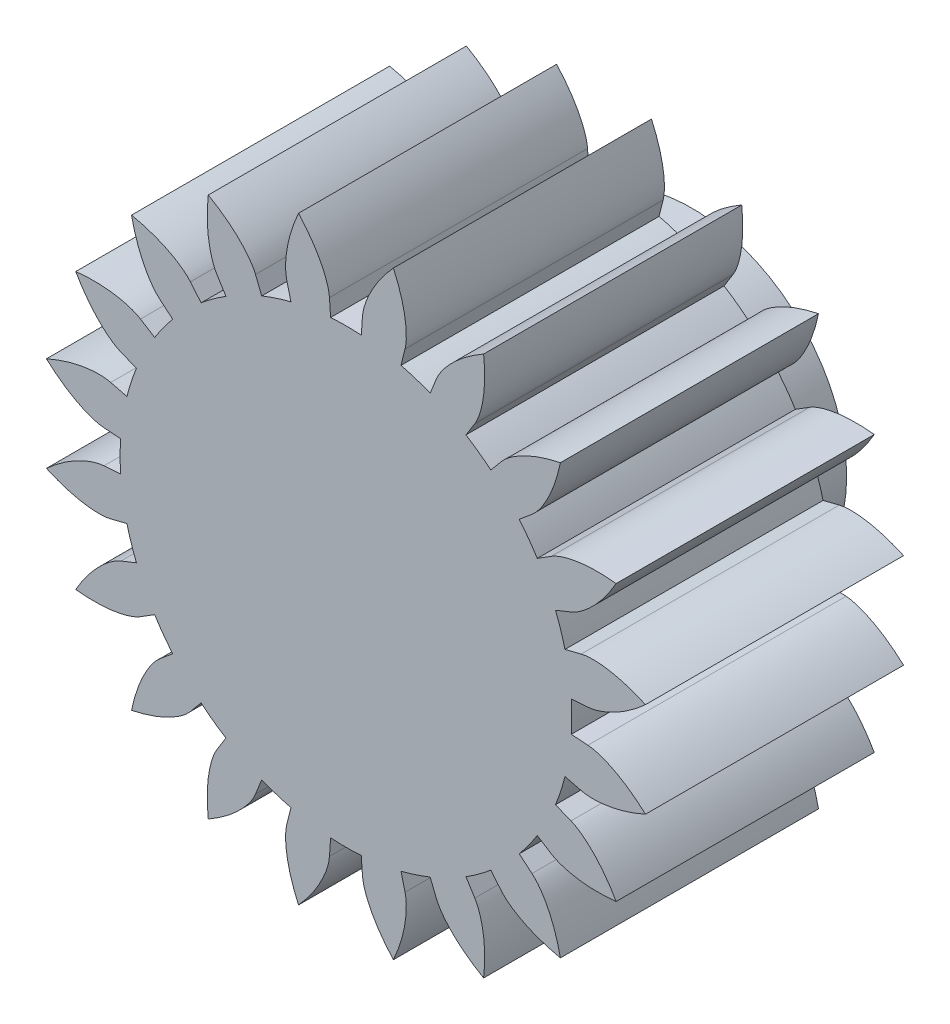
SolidWorks part; units mm, degrees
ref_plane "前视基准面" through (0, 0, 0) normal (0, 0, 1) x (1, 0, 0)
ref_plane "上视基准面" through (0, 0, 0) normal (0, 1, 0) x (1, 0, 0)
ref_plane "右视基准面" through (0, 0, 0) normal (1, 0, 0) x (0, 0, -1)
other "Configuration Table"
sketch "草图1" plane through (0, 0, 0) normal (0, 0, 1) x (1, 0, 0)
  line L0 (0, 0) -> (5, 0) construction
  line L1 (0, 0) -> (4.9846, 0.3923) construction
  line L2 (0, 0) -> (4.6876, 0.3194)
  line L3 (4.9846, 0.3923) -> (4.9846, -0.3923) construction
  line L4 (0, 0) -> (4.6876, -0.3194)
  circle A0 centre (0, 0) radius 5.5
  circle A1 centre (0, 0) radius 5 construction
  circle A2 centre (0, 0) radius 4.375
  circle A3 centre (0, 0) radius 4.6985 construction
  circle A4 centre (0, 0) radius 1.475
  circle A5 centre (0, 0) radius 6.5
  spline S0 degree 4 poles (4.6876, 0.3194) (4.7233, 0.3218) (4.8225, 0.336) (5.0062, 0.3926) (5.2885, 0.5242) (5.6241, 0.7499) (6.0094, 1.0976) (6.395, 1.5688) (6.7398, 2.1414) (7.0933, 2.9696) (7.3065, 3.8467) (7.3947, 4.7795) (7.347, 5.8934) (7.1568, 6.9938) (6.7515, 8.227) (6.0949, 9.5107) (5.2611, 10.6861) (4.2765, 11.7378) (3.1662, 12.6551) (1.9531, 13.4307) (0.6586, 14.0604) (-0.5283, 14.4821) (-1.4854, 14.7287) (-2.1912, 14.8654) (-2.6338, 14.9356) (-2.9917, 14.9827) (-3.3451, 15.0208) (-3.7095, 15.05) (-4.0266, 15.0684) (-4.3306, 15.0786) (-4.6986, 15.0842) (-4.9527, 15.0816) (-5.4001, 15.0704) (-5.6957, 15.0494) (-6.0237, 15.027) (-6.2862, 14.9991) (-6.5922, 14.9657) (-6.7961, 14.9366) (-6.9439, 14.9154) (-7.0152, 14.9043) knots 0 0 0 0 0 0.005604 0.015718 0.02996 0.048734 0.068727 0.096889 0.125051 0.153212 0.209535 0.237696 0.271429 0.327752 0.384075 0.440398 0.496721 0.553044 0.609367 0.66569 0.722013 0.778336 0.806497 0.820578 0.834659 0.84874 0.86282 0.876901 0.890982 0.900036 0.909091 0.931818 0.943182 0.954545 0.965909 0.977273 0.988636 1 1 1 1 1 construction
  spline S1 degree 4 poles (4.6876, 0.3194) (4.7233, 0.3218) (4.8225, 0.336) (5.0062, 0.3926) (5.2885, 0.5242) (5.6241, 0.7499) (6.0094, 1.0976) (6.395, 1.5688) (6.7398, 2.1414) (7.0933, 2.9696) (7.3065, 3.8467) (7.3947, 4.7795) (7.347, 5.8934) (7.1568, 6.9938) (6.7515, 8.227) (6.0949, 9.5107) (5.2611, 10.6861) (4.2765, 11.7378) (3.1662, 12.6551) (1.9531, 13.4307) (0.6586, 14.0604) (-0.5283, 14.4821) (-1.4854, 14.7287) (-2.1912, 14.8654) (-2.6338, 14.9356) (-2.9917, 14.9827) (-3.3451, 15.0208) (-3.7095, 15.05) (-4.0266, 15.0684) (-4.3306, 15.0786) (-4.5463, 15.0819) (-4.6529, 15.0825) (-4.7054, 15.0825) knots 0 0 0 0 0 0.005604 0.015718 0.02996 0.048734 0.068727 0.096889 0.125051 0.153212 0.209535 0.237696 0.271429 0.327752 0.384075 0.440398 0.496721 0.553044 0.609367 0.66569 0.722013 0.778336 0.806497 0.820578 0.834659 0.84874 0.86282 0.876901 0.890982 0.900036 0.909091 0.909091 0.909091 0.909091 0.909091
  spline S2 degree 4 poles (4.6876, -0.3194) (4.7233, -0.3218) (4.8225, -0.336) (5.0062, -0.3926) (5.2885, -0.5242) (5.6241, -0.7499) (6.0094, -1.0976) (6.395, -1.5688) (6.7398, -2.1414) (7.0933, -2.9696) (7.3065, -3.8467) (7.3947, -4.7795) (7.347, -5.8934) (7.1568, -6.9938) (6.7515, -8.227) (6.0949, -9.5107) (5.2611, -10.6861) (4.2765, -11.7378) (3.1662, -12.6551) (1.9531, -13.4307) (0.6586, -14.0604) (-0.5283, -14.4821) (-1.4854, -14.7287) (-2.1912, -14.8654) (-2.6338, -14.9356) (-2.9917, -14.9827) (-3.3451, -15.0208) (-3.7095, -15.05) (-4.0266, -15.0684) (-4.3306, -15.0786) (-4.6986, -15.0842) (-4.9527, -15.0816) (-5.4001, -15.0704) (-5.6957, -15.0494) (-6.0237, -15.027) (-6.2862, -14.9991) (-6.5922, -14.9657) (-6.7961, -14.9366) (-6.9439, -14.9154) (-7.0152, -14.9043) knots 0 0 0 0 0 0.005604 0.015718 0.02996 0.048734 0.068727 0.096889 0.125051 0.153212 0.209535 0.237696 0.271429 0.327752 0.384075 0.440398 0.496721 0.553044 0.609367 0.66569 0.722013 0.778336 0.806497 0.820578 0.834659 0.84874 0.86282 0.876901 0.890982 0.900036 0.909091 0.931818 0.943182 0.954545 0.965909 0.977273 0.988636 1 1 1 1 1 construction
  spline S3 degree 4 poles (4.6876, -0.3194) (4.7233, -0.3218) (4.8225, -0.336) (5.0062, -0.3926) (5.2885, -0.5242) (5.6241, -0.7499) (6.0094, -1.0976) (6.395, -1.5688) (6.7398, -2.1414) (7.0933, -2.9696) (7.3065, -3.8467) (7.3947, -4.7795) (7.347, -5.8934) (7.1568, -6.9938) (6.7515, -8.227) (6.0949, -9.5107) (5.2611, -10.6861) (4.2765, -11.7378) (3.1662, -12.6551) (1.9531, -13.4307) (0.6586, -14.0604) (-0.5283, -14.4821) (-1.4854, -14.7287) (-2.1912, -14.8654) (-2.6338, -14.9356) (-2.9917, -14.9827) (-3.3451, -15.0208) (-3.7095, -15.05) (-4.0266, -15.0684) (-4.3306, -15.0786) (-4.5463, -15.0819) (-4.6529, -15.0825) (-4.7054, -15.0825) knots 0 0 0 0 0 0.005604 0.015718 0.02996 0.048734 0.068727 0.096889 0.125051 0.153212 0.209535 0.237696 0.271429 0.327752 0.384075 0.440398 0.496721 0.553044 0.609367 0.66569 0.722013 0.778336 0.806497 0.820578 0.834659 0.84874 0.86282 0.876901 0.890982 0.900036 0.909091 0.909091 0.909091 0.909091 0.909091
  point P15 (4.9846, 0)
  dimension "齿顶圆直径" = 11
  dimension "分度圆直径" = 10
  dimension "齿根圆直径" = 8.75
  dimension "基圆直径" = 9.3969
  dimension "内孔直径" = 2.95
  dimension "渐近线镜像线夹角" = 4.5
  dimension "D1" = 1
extrude "凸台-拉伸1" add sketch "草图1" along normal blind 5 contours A0 | A4
sketch "草图6" plane through (0, 0, 0) normal (0, 0, -1) x (-1, 0, 0)
  circle A0 centre (0, 0) radius 6
  circle A1 centre (0, 0) radius 5.5 construction
  circle M1 centre (0, 0) radius 5.5
  dimension "D1" = 0.5
extrude "凸台-拉伸4" add sketch "草图6" against normal up to surface (5 mm away) contours A0 M1 region at (5.8303, 0, 0) up to face at (5.5, 0, 5)
extrude "切除-拉伸1" cut sketch "草图1<3>" along normal through all contours A2 S3 A0 S1 | A0 S3 A5 S1 region at (5.0102, 0, 0) region at (6.0346, 0, 0)
sketch "草图1<3>" plane through (0, 0, 0) normal (0, 0, 1) x (1, 0, 0) same geometry as "草图1"
pattern_circular "阵列(圆周)1" count 20 every 18 about axis through (0, 0, 5) along (0, 0, -1) of "切除-拉伸1"
sketch "草图2" plane through (0, 0, 5) normal (0, 0, 1) x (1, 0, 0)
  circle A0 centre (0, 0) radius 1.475
extrude "凸台-拉伸2" add sketch "草图2" against normal through all
sketch "草图3" plane through (0, 0, 0) normal (0, 0, -1) x (-1, 0, 0)
  line L7 (-1, 0.25) -> (1, 0.25)
  line L8 (-1, 0.25) -> (-1, -0.25)
  line L9 (-1, -0.25) -> (1, -0.25)
  line L10 (1, 0.25) -> (1, -0.25)
  line L11 (-0.25, 1) -> (0.25, 1)
  line L12 (-0.25, 1) -> (-0.25, -1)
  line L13 (-0.25, -1) -> (0.25, -1)
  line L14 (0.25, 1) -> (0.25, -1)
  circle A0 centre (0, 0) radius 2
  circle A1 centre (0, 0) radius 3
  point P13 (0, 1)
  point P14 (-0.25, 0)
  point P15 (-1, 0)
  point P16 (0, 0.25)
  dimension "D1" = 1
  dimension "D2" = 4
  dimension "D3" = 2
  dimension "D4" = 0.5
extrude "凸台-拉伸3" add sketch "草图3" along normal blind 1.7 contours A1 A0 | L9 L10 L7 L8 | L12 L13 L14 L11 region at (2.9151, 0, 0)
sketch "草图4" plane through (0, 0, 5) normal (0, 0, 1) x (1, 0, 0)
  line L0 (1, 1.118) -> (1, -1.118)
  circle A0 centre (0, 0) radius 1.5
  dimension "D1" = 3
  dimension "D2" = 1
sketch "草图5" plane through (0, 0, -1.7) normal (0, 0, -1) x (-1, 0, 0)
  circle A0 centre (0, 0) radius 2
  circle A1 centre (0, 0) radius 2 construction
extrude "切除-拉伸2" cut sketch "草图5" against normal blind 1
equation "\"m\"= 0.5'模数"
equation "\"z\"= 20'齿数"
equation "\"a\"= 20度'压力角"
equation "\"d\"= \"m\" * \"z\"'分度圆直径"
equation "\"da\"= ( \"z\" + 2 ) * \"m\"'齿顶圆直径"
equation "\"df\"= ( \"z\" - 2.5 ) * \"m\"'齿根圆直径"
equation "\"s\"= 0.5 * PI * \"m\"'分度圆齿厚"
equation "\"r\"= 0.38 * \"m\"'齿根圆角"
equation "\"B\"= 0.3 * \"d\"'齿厚"
equation "\"db\"= \"m\" * \"z\" * cos ( \"a\" )'基圆直径"
equation "\"rb\"= \"db\" / 2'基圆半径"
equation "\"齿顶圆直径@草图1\"= \"da\""
equation "\"分度圆直径@草图1\"= \"d\""
equation "\"齿根圆直径@草图1\"= \"df\""
equation "\"基圆直径@草图1\"= \"db\""
equation "\"渐近线镜像线夹角@草图1\"= 360 / 4 / \"z\""
equation "\"h\"= 5'齿轮厚度"
equation "\"ir\"= 2.95'内孔直径"
equation "\"内孔直径@草图1\"= \"ir\""
equation "\"齿轮厚@凸台-拉伸1\"= \"h\""
equation "\"齿轮夹角@阵列(圆周)1\"= 360 / \"z\""
equation "\"齿数@阵列(圆周)1\"= \"z\""
